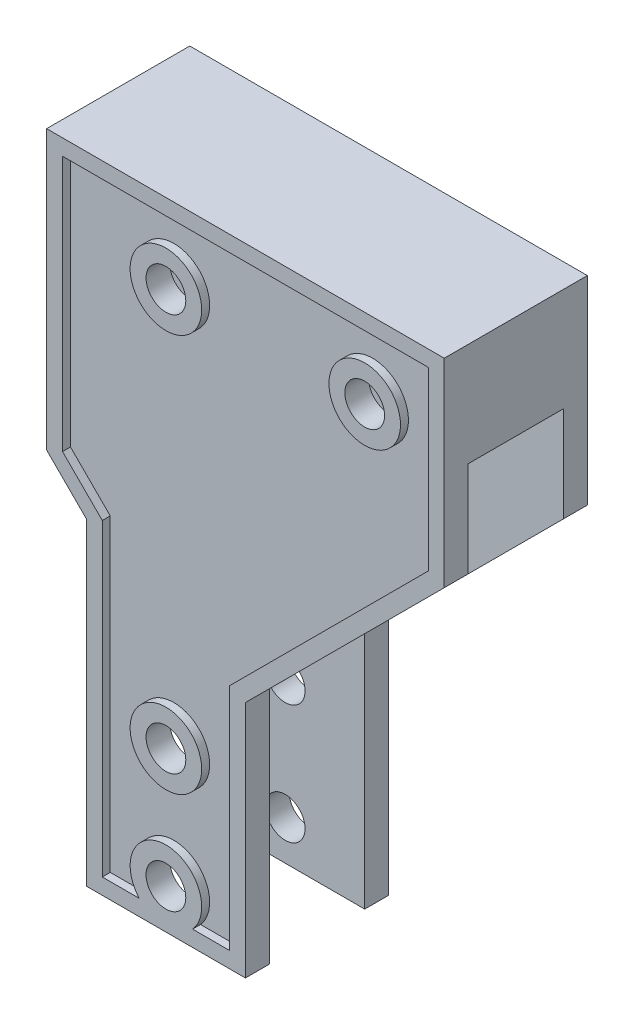
SolidWorks part; units mm, degrees
ref_plane "Plan de face" through (0, 0, 0) normal (0, 0, 1) x (1, 0, 0)
ref_plane "Plan de dessus" through (0, 0, 0) normal (0, 1, 0) x (1, 0, 0)
ref_plane "Plan de droite" through (0, 0, 0) normal (1, 0, 0) x (0, 0, -1)
sketch "Esquisse1" plane through (0, 0, 0) normal (0, 0, 1) x (1, 0, 0)
  line L0 (-45, 40) -> (-50, 45)
  line L1 (-50, 80) -> (0, 80)
  line L2 (-50, 80) -> (-50, 0)
  line L3 (-50, 0) -> (0, 0)
  line L4 (0, 80) -> (0, 0)
  line L5 (-45, 40) -> (-45, 0)
  line L7 (-25, 0) -> (-25, 30)
  line L8 (-25, 30) -> (0, 55)
  circle A0 centre (-35, 5) radius 2.5
  circle A1 centre (-35, 20) radius 2.5
  dimension "D7" = 5
  dimension "D9" = 5
  dimension "D1" = 80
  dimension "D2" = 50
  dimension "D3" = 40
  dimension "D4" = 30
  dimension "D5" = 5
  dimension "D6" = 5
  dimension "D8" = 15
  dimension "D10" = 10
  dimension "D11" = 10
  dimension "D13" = 135
  dimension "D14" = 135
  dimension "D15" = 25
extrude "Boss.-Extru.1" add sketch "Esquisse1" along normal blind 18 contours L7 L8 L4 L1 L2 L0 L5 L3 A1 A0 region at (-28.4996, 49.059, 0)
shell "Coque2" thickness 3 removed face at (-32.5, 20, 18) removed face at (-32.5, 5, 18) removed face at (-25, 15, 9) removed face at (-45, 20, 9) removed face at (-35, 0, 9) removed face at (-12.5, 42.5, 9) removed face at (-47.5, 42.5, 9)
sketch "Esquisse2" plane through (-45, 0, 0) normal (-1, 0, 0) x (0, 0, 1)
  line L0 (3, 77) -> (3, 52) construction
  line L1 (15, 52) -> (3, 52)
  line L2 (15, 52) -> (15, 67)
  line L3 (15, 67) -> (3, 67)
  line L4 (3, 52) -> (3, 67)
  dimension "D1" = 15
extrude "Enlèv. mat.-Extru.1" cut sketch "Esquisse2" against normal through all both and the other way through all
sketch "Esquisse3" plane through (0, 0, 18) normal (0, 0, 1) x (1, 0, 0)
  line L1 (-50, 80) -> (-50, 45) construction
  line L2 (-50, 80) -> (0, 80) construction
  line L3 (0, 80) -> (0, 55) construction
  circle A0 centre (-35, 70) radius 2.5
  circle A1 centre (-10, 70) radius 2.5
  dimension "D1" = 5
  dimension "D4" = 5
  dimension "D2" = 15
  dimension "D3" = 10
  dimension "D5" = 10
  dimension "D6" = 10
extrude "Enlèv. mat.-Extru.3" cut sketch "Esquisse3" against normal through all
shell "Shell2" thickness 2 removed face at (-32.5, 70, 0) removed face at (-32.5, 70, 18)
